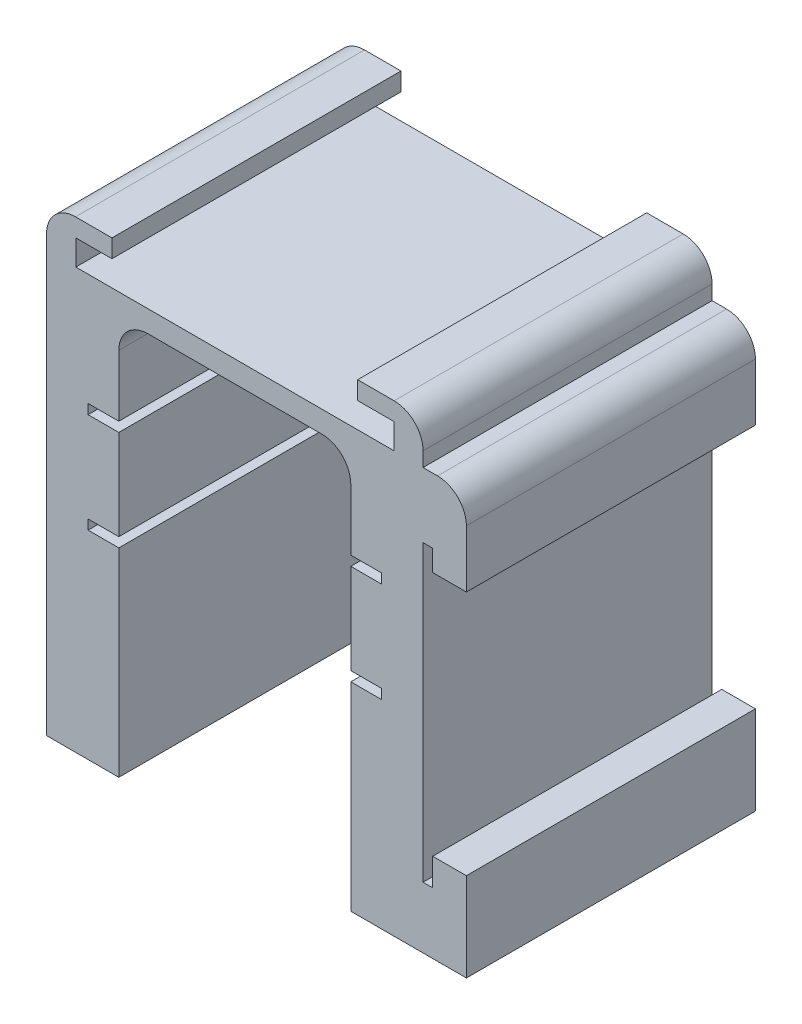
SolidWorks part; units mm, degrees
ref_plane "Front Plane" through (0, 0, 0) normal (0, 0, 1) x (1, 0, 0)
ref_plane "Top Plane" through (0, 0, 0) normal (0, 1, 0) x (1, 0, 0)
ref_plane "Right Plane" through (0, 0, 0) normal (1, 0, 0) x (0, 0, -1)
sketch "Sketch1" plane through (0, 0, 0) normal (0, 0, 1) x (1, 0, 0)
  line L1 (12.7, 70.0786) -> (12.7, 54.2036)
  line L2 (12.7, 54.2036) -> (7.3025, 54.2036)
  line L3 (7.3025, 54.2036) -> (7.3025, 52.5018)
  line L4 (7.3025, 52.5018) -> (12.7, 52.5018)
  line L5 (12.7, 52.5018) -> (12.7, 36.6268)
  line L6 (12.7, 36.6268) -> (7.3025, 36.6268)
  line L7 (7.3025, 36.6268) -> (7.3025, 34.925)
  line L8 (7.3025, 34.925) -> (12.7, 34.925)
  line L9 (12.7, 34.925) -> (12.7, 0)
  line L10 (12.7, 0) -> (0, 0)
  line L11 (0, 0) -> (0, 73.8886)
  line L13 (12.7, 70.0786) -> (53.467, 70.0786)
  line L15 (0, 73.8886) -> (66.167, 73.8886)
  line L16 (33.0835, 70.0786) -> (33.0835, 73.8886) construction
  line L17 (66.167, 10.7696) -> (66.167, 62.4586)
  line L18 (53.467, 0) -> (66.167, 0)
  line L19 (53.467, 34.925) -> (53.467, 0)
  line L20 (58.8645, 34.925) -> (53.467, 34.925)
  line L21 (58.8645, 36.6268) -> (58.8645, 34.925)
  line L22 (53.467, 36.6268) -> (58.8645, 36.6268)
  line L23 (53.467, 52.5018) -> (53.467, 36.6268)
  line L24 (58.8645, 52.5018) -> (53.467, 52.5018)
  line L25 (58.8645, 54.2036) -> (58.8645, 52.5018)
  line L26 (53.467, 54.2036) -> (58.8645, 54.2036)
  line L27 (53.467, 70.0786) -> (53.467, 54.2036)
  line L29 (66.167, 73.8886) -> (73.787, 73.8886)
  line L30 (66.167, 62.4586) -> (66.167, 10.7696)
  line L31 (66.167, 0) -> (73.787, 0)
  line L32 (73.787, 73.8886) -> (73.787, 58.7526)
  line L33 (67.8688, 58.7526) -> (66.167, 58.7526) construction
  line L34 (73.787, 58.7526) -> (67.8688, 58.7526)
  line L35 (73.787, 58.7526) -> (73.787, 15.5726) construction
  line L36 (73.787, 15.5726) -> (67.8688, 15.5726)
  line L37 (66.167, 58.7526) -> (66.167, 15.5726)
  line L38 (66.167, 62.4586) -> (67.8688, 62.4586)
  line L39 (66.167, 62.4586) -> (66.167, 10.7696)
  line L40 (66.167, 10.7696) -> (67.8688, 10.7696)
  line L41 (67.8688, 62.4586) -> (67.8688, 58.7526)
  line L42 (73.787, 58.7526) -> (73.787, 15.5726) construction
  line L43 (73.787, 15.5726) -> (73.787, 0)
  line L44 (67.8688, 58.7526) -> (67.8688, 15.5726) construction
  line L45 (67.8688, 15.5726) -> (67.8688, 10.7696)
  line L46 (67.8688, 15.5726) -> (66.167, 15.5726) construction
  line L47 (66.167, 62.4586) -> (66.167, 73.8886) construction
  line L48 (66.167, 73.8886) -> (66.167, 62.4586) construction
  line L49 (66.167, 0) -> (66.167, 10.7696) construction
  line L50 (66.167, 10.7696) -> (66.167, 0) construction
  line L51 (33.0835, -926.1114) -> (33.0835, 49073.8886) construction
  line L52 (0, 73.8886) -> (5.1435, 73.8886)
  line L53 (0, 73.8886) -> (0, 81.5086)
  line L54 (0, 81.5086) -> (5.1435, 81.5086)
  line L55 (5.1435, 73.8886) -> (5.1435, 78.3336)
  line L56 (5.1435, 81.5086) -> (11.4935, 81.5086)
  line L57 (5.1435, 81.5086) -> (5.1435, 78.3336) construction
  line L58 (5.1435, 78.3336) -> (11.4935, 78.3336)
  line L59 (11.4935, 81.5086) -> (11.4935, 78.3336)
  line L60 (5.1435, 78.3336) -> (5.1435, 81.5086) construction
  line L61 (61.0235, 73.8886) -> (61.0235, 78.3336)
  line L62 (61.0235, 78.3336) -> (54.6735, 78.3336)
  line L63 (66.167, 73.8886) -> (66.167, 81.5086)
  line L64 (66.167, 81.5086) -> (61.0235, 81.5086)
  line L65 (61.0235, 81.5086) -> (54.6735, 81.5086)
  line L66 (54.6735, 81.5086) -> (54.6735, 78.3336)
  dimension "D1" = 1.7018
  dimension "D2" = 1.7018
  dimension "D3" = 5.3975
  dimension "D4" = 12.7
  dimension "D5" = 34.925
  dimension "D6" = 15.875
  dimension "D7" = 15.875
  dimension "D8" = 25.781
  dimension "D9" = 3.81
  dimension "D10" = 7.62
  dimension "D11" = 43.18
  dimension "D12" = 7.62
  dimension "D13" = 51.689
  dimension "D14" = 1.7018
  dimension "D15" = 11.43
  dimension "D16" = 7.62
  dimension "D18" = 6.35
  dimension "D19" = 3.175
  dimension "D17" = 43.18
extrude "Boss-Extrude1" add sketch "Sketch1" along normal blind 50.8 contours L36 L45 L40 L17 L30 L38 L41 L34 L32 L29 L15 L11 L10 L9 L8 L7 L6 L5 L4 L3 L2 L1 L13 L27 L26 L25 L24 L23 L22 L21 L20 L19 L18 L31 L43 | L59 L56 L54 L53 L15 L55 L58 | L65 L66 L62 L61 L15 L63 L64 region at (11.6558, 62.1411, 0) region at (4.5238, 78.4535, 0) region at (61.6432, 78.4535, 0)
sketch "Sketch2" plane through (0, 0, 0) normal (0, -1, 0) x (1, 0, 0)
  line L0 (12.7, 50.8) -> (0, 50.8) construction
  line L2 (0, 50.8) -> (0, 0) construction
  line L3 (73.787, 50.8) -> (73.787, 0) construction
  line L4 (53.467, 0) -> (73.787, 0) construction
  circle A0 centre (6.35, 44.45) radius 2.6035
  circle A1 centre (67.437, 6.35) radius 2.6035
  point P2 (0, 0)
  dimension "D1" = 5.207
  dimension "D4" = 5.207
  dimension "D2" = 6.35
  dimension "D3" = 6.35
  dimension "D5" = 6.35
  dimension "D6" = 6.35
extrude "Cut-Extrude1" cut sketch "Sketch2" against normal blind 5.08
fillet "Fillet1" radius 5.08 5 edges at (73.787, 73.8886, 25.4) (66.167, 81.5086, 25.4) (0, 81.5086, 25.4) (53.467, 70.0786, 25.4) (12.7, 70.0786, 25.4)
equation "\"DUALTB_T\"= 0.062in"
equation "\"TightTol\"= 0.005in"
equation "\"D1@Sketch1\"=\"DUALTB_T\" + \"TightTol\" "
equation "\"D2@Sketch1\"=\"DUALTB_T\" + \"TightTol\""
